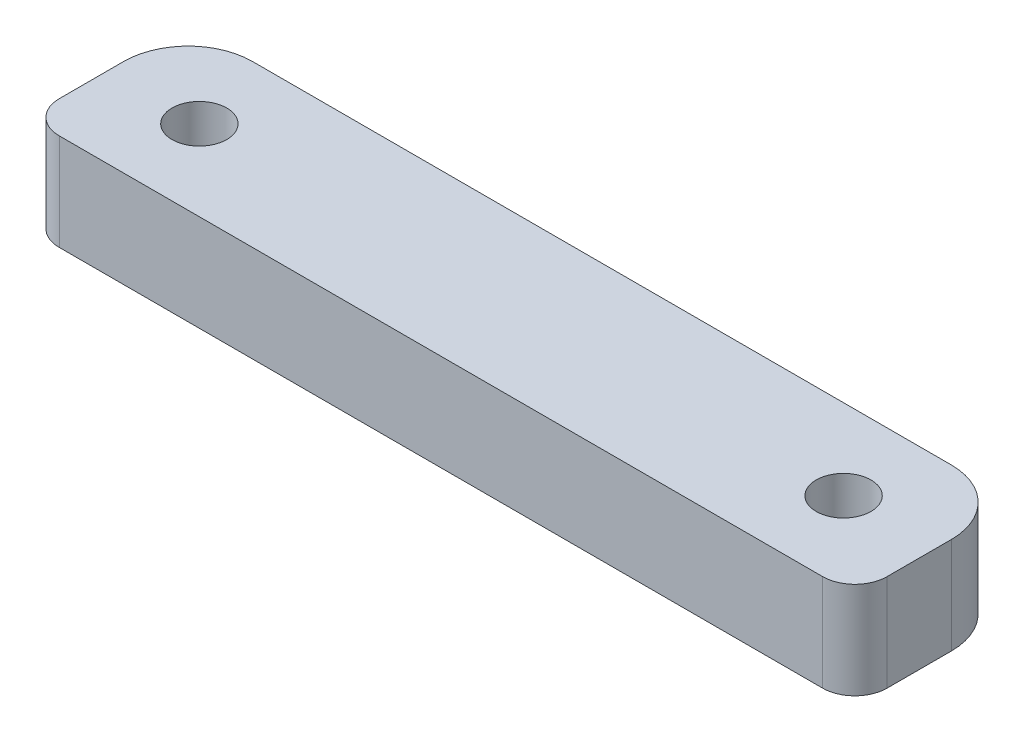
SolidWorks part; units mm, degrees
ref_plane "Front Plane" through (0, 0, 0) normal (0, 0, 1) x (1, 0, 0)
ref_plane "Top Plane" through (0, 0, 0) normal (0, 1, 0) x (1, 0, 0)
ref_plane "Right Plane" through (0, 0, 0) normal (1, 0, 0) x (0, 0, -1)
sketch "Sketch1" plane through (0, 0, 0) normal (0, 1, 0) x (1, 0, 0)
  line L0 (-25.7, 0) -> (25.7, 0) construction
  line L1 (-25.7, -5) -> (25.7, -5)
  line L2 (-25.7, -5) -> (-25.7, 5)
  line L3 (-25.7, 5) -> (25.7, 5)
  line L4 (25.7, -5) -> (25.7, 5)
  line L5 (-25.7, -5) -> (25.7, 5) construction
  line L6 (-25.7, 5) -> (25.7, -5) construction
  line L7 (0, 0) -> (0, 5) construction
  line L9 (-2.65, -2.2) -> (2.65, -2.2)
  line L10 (-2.65, -2.2) -> (-2.65, 5)
  line L11 (-2.65, 5) -> (2.65, 5)
  line L12 (2.65, -2.2) -> (2.65, 5)
  line L13 (-2.65, -2.2) -> (2.65, 5) construction
  line L14 (-2.65, 5) -> (2.65, -2.2) construction
  circle A0 centre (-20, 0) radius 1.7
  circle A1 centre (20, 0) radius 1.7
  point P0 (0, 0)
  point P14 (0, 1.4)
  dimension "D3" = 3.4
  dimension "D1" = 10
  dimension "D2" = 40
  dimension "D4" = 5.7
  dimension "D5" = 5.3
  dimension "D6" = 7.2
extrude "Boss-Extrude2" add sketch "Sketch1" along normal blind 6 contours L12 L9 L10 L3 L2 L1 L4 A0 A1 | L9 L12 L3 L10 region at (-25.1764, 0, 0) region at (0, 0, -1.4)
extrude "Cut-Extrude1" cut sketch "Sketch1<4>" along normal blind 3.8 contours L9 L12 L3 L10 region at (0, 0, -1.4)
sketch "Sketch1<4>" plane through (0, 0, 0) normal (0, 1, 0) x (1, 0, 0) same geometry as "Sketch1"
fillet "Fillet2" radius 4 2 edges at (25.7, 3, -5) (-25.7, 3, -5)
fillet "Fillet3" radius 2 2 edges at (25.7, 3, 5) (-25.7, 3, 5)
